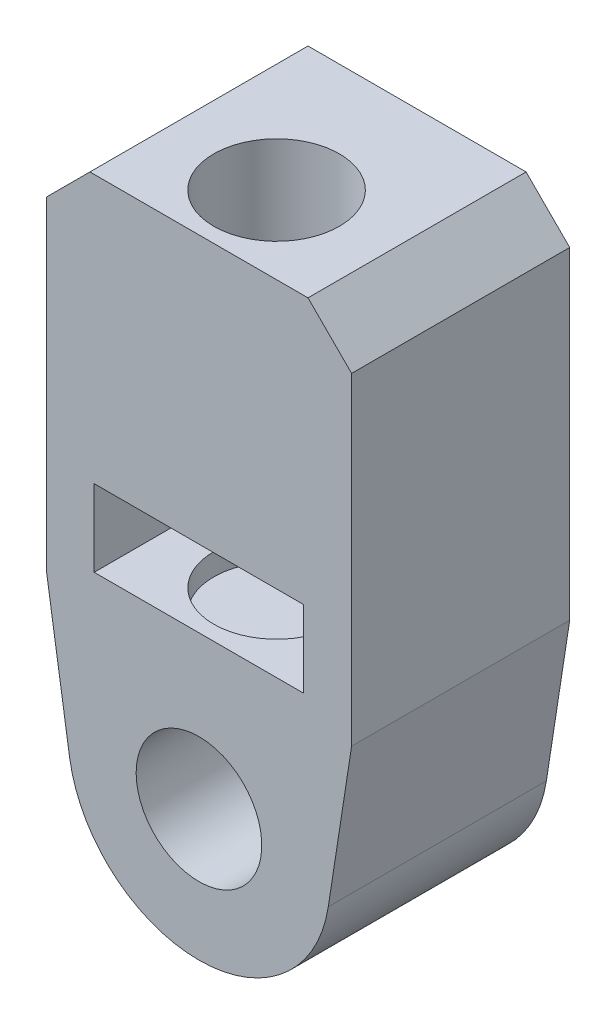
SolidWorks part; units mm, degrees
ref_plane "Front Plane" through (0, 0, 0) normal (0, 0, 1) x (1, 0, 0)
ref_plane "Top Plane" through (0, 0, 0) normal (0, 1, 0) x (1, 0, 0)
ref_plane "Right Plane" through (0, 0, 0) normal (1, 0, 0) x (0, 0, -1)
sketch "Sketch1" plane through (0, 0, 0) normal (0, 0, 1) x (1, 0, 0)
  line L0 (-5.5562, 4.7625) -> (-5.5562, 18.0975)
  line L1 (-5.5562, 18.0975) -> (5.5562, 18.0975)
  line L2 (5.5562, 18.0975) -> (5.5562, 4.7625)
  line L3 (-5.5562, 4.7625) -> (-4.7065, -0.7284)
  line L4 (4.7065, -0.7284) -> (5.5562, 4.7625)
  circle A1 centre (0, 0) radius 2.286
  arc A2 (-4.7065, -0.7284) -> (4.7065, -0.7284) centre (0, 0) ccw
  point P10 (0, 18.0975)
  dimension "D1" = 9.525
  dimension "D2" = 4.572
  dimension "D3" = 13.335
  dimension "D4" = 11.1125
  dimension "D5" = 4.7625
extrude "Boss-Extrude1" add sketch "Sketch1" along normal up to surface (7.9375 mm away)
sketch "Sketch2" plane through (0, 18.0975, 0) normal (0, 1, 0) x (1, 0, 0)
  circle A1 centre (0, -5.1125) radius 2.286
  circle A2 centre (0, -5.1125) radius 1.7525 construction
  dimension "D1" = 4.572
extrude "Cut-Extrude1" cut sketch "Sketch2" against normal offset from surface (13.335 mm away) 4.7625 up to plane "Top Plane"
sketch "Sketch3" plane through (0, 4.7625, 0) normal (0, 1, 0) x (1, 0, 0)
  line L11 (5.5562, -7.9375) -> (-5.5562, -7.9375) construction
  line L12 (-1.9064, -1.8105) -> (-3.8128, -5.1125)
  line L16 (3.8128, -5.1125) -> (1.9064, -1.8105)
  line L17 (1.9064, -1.8105) -> (-1.9064, -1.8105)
  line L18 (-3.8128, -5.1125) -> (-3.8128, -7.9375)
  line L19 (-3.8128, -7.9375) -> (3.8128, -7.9375)
  line L20 (3.8128, -7.9375) -> (3.8128, -5.1125)
  line L22 (-1.9064, -8.4145) -> (0, -8.4145) [skipped]
  line L23 (-3.8128, -5.1125) -> (-2.8596, -6.7635) [skipped]
  line L24 (2.1818, -7.9375) -> (2.8596, -6.7635) [skipped]
  circle A0 centre (0, -5.1125) radius 3.302 construction
  dimension "D1" = 6.604
extrude "Cut-Extrude2" cut sketch "Sketch3" along normal blind 2.794 from offset 0.7937
chamfer "Chamfer1" distance 1.5875 angle 45 2 edges at (5.5562, 18.0975, 3.9687) (-5.5562, 18.0975, 3.9687)
